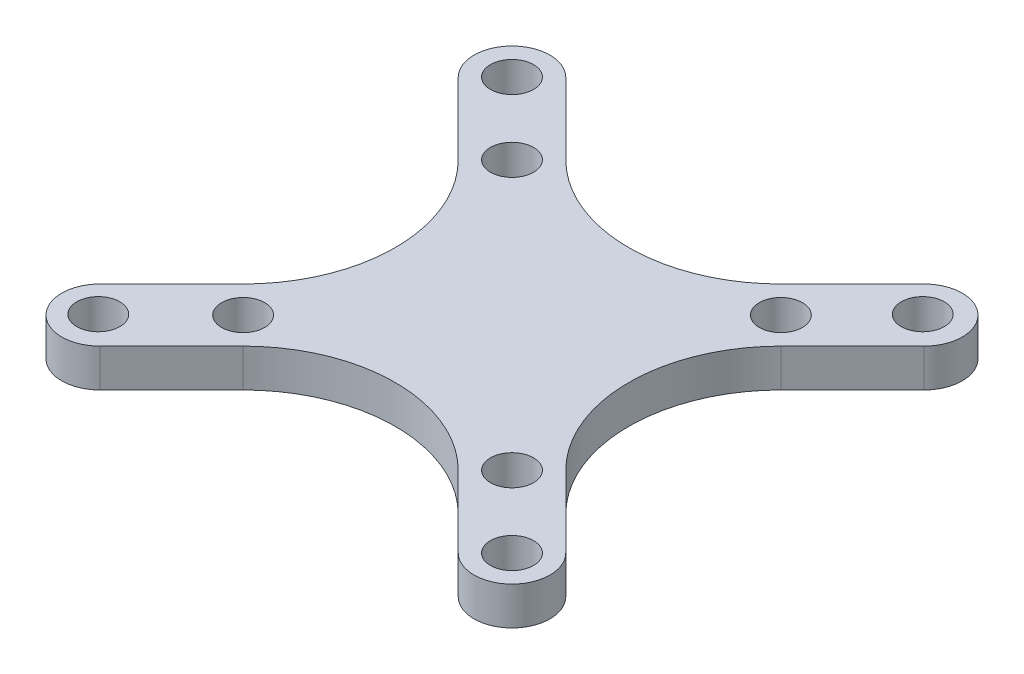
SolidWorks part; units mm, degrees
ref_plane "Front Plane" through (0, 0, 0) normal (0, 0, 1) x (1, 0, 0)
ref_plane "Top Plane" through (0, 0, 0) normal (0, 1, 0) x (1, 0, 0)
ref_plane "Right Plane" through (0, 0, 0) normal (1, 0, 0) x (0, 0, -1)
sketch "Sketch1" plane through (0, 0, 0) normal (0, 1, 0) x (1, 0, 0)
  line L0 (-16.2635, 16.2635) -> (16.2635, -16.2635) construction
  line L1 (16.1474, 16.2635) -> (-16.3795, -16.2635) construction
  line L2 (-18.3848, 14.1421) -> (-12.7279, 8.4853)
  line L3 (14.1421, 18.3848) -> (8.4853, 12.7279)
  line L4 (-14.1421, 18.3848) -> (-8.4853, 12.7279)
  line L5 (18.3848, 14.1421) -> (12.7279, 8.4853)
  line L6 (-12.7279, -8.4853) -> (-18.3848, -14.1421)
  line L7 (8.4853, -12.7279) -> (14.1421, -18.3848)
  line L8 (-8.4853, -12.7279) -> (-14.1421, -18.3848)
  line L9 (12.7279, -8.4853) -> (18.3848, -14.1421)
  line L10 (-18.3848, 18.3848) -> (-35, 35) construction
  line L11 (-25, -35) -> (25, -35)
  line L12 (-35, -25) -> (-35, 25)
  line L13 (-25, 35) -> (25, 35)
  line L14 (35, -25) -> (35, 25)
  line L15 (-35, -35) -> (35, 35) construction
  line L16 (-35, 35) -> (35, -35) construction
  line L17 (0, 35) -> (-21.6769, 28.2534)
  line L18 (-28.2534, 21.6769) -> (-35, 0)
  line L19 (-18.3848, -18.3848) -> (-35, -35) construction
  line L20 (35, -35) -> (18.3848, -18.3848) construction
  line L21 (35, 35) -> (18.3848, 18.3848) construction
  line L22 (-35, 0) -> (-28.2534, -21.6769)
  line L23 (-21.6769, -28.2534) -> (0, -35)
  line L24 (0, -35) -> (21.6769, -28.2534)
  line L25 (28.2534, -21.6769) -> (35, 0)
  line L26 (35, 0) -> (28.2534, 21.6769)
  line L27 (21.6769, 28.2534) -> (0, 35)
  circle A0 centre (-16.3795, -16.2635) radius 1.7
  circle A1 centre (-10.6066, -10.6066) radius 1.7
  circle A2 centre (16.2635, -16.2635) radius 1.7
  circle A3 centre (10.6066, -10.6066) radius 1.7
  circle A16 centre (16.1474, 16.2635) radius 1.7
  circle A17 centre (10.6066, 10.6066) radius 1.7
  circle A18 centre (-16.2635, 16.2635) radius 1.7
  circle A19 centre (-10.6066, 10.6066) radius 1.7
  arc A20 (-18.3848, 14.1421) -> (-14.1421, 18.3848) centre (-16.2635, 16.2635) cw
  arc A21 (14.1421, 18.3848) -> (18.3848, 14.1421) centre (16.2635, 16.2635) cw
  arc A22 (14.1421, -18.3848) -> (18.3848, -14.1421) centre (16.2635, -16.2635) ccw
  arc A23 (-14.1421, -18.3848) -> (-18.3848, -14.1421) centre (-16.2635, -16.2635) cw
  arc A24 (8.4853, 12.7279) -> (-8.4853, 12.7279) centre (0, 21.2132) cw
  arc A25 (-12.7279, -8.4853) -> (-12.7279, 8.4853) centre (-21.2132, 0) ccw
  arc A26 (12.7279, 8.4853) -> (12.7279, -8.4853) centre (21.2132, 0) ccw
  arc A27 (8.4853, -12.7279) -> (-8.4853, -12.7279) centre (0, -21.2132) ccw
  arc A29 (-25, -35) -> (-35, -25) centre (-25, -25) cw
  arc A30 (25, -35) -> (35, -25) centre (25, -25) ccw
  arc A31 (25, 35) -> (35, 25) centre (25, 25) cw
  arc A32 (-35, 25) -> (-25, 35) centre (-25, 25) cw
  arc A33 (-28.2534, -21.6769) -> (-21.6769, -28.2534) centre (-18.7052, -18.7052) ccw
  arc A34 (21.6769, -28.2534) -> (28.2534, -21.6769) centre (18.7052, -18.7052) ccw
  arc A35 (28.2534, 21.6769) -> (21.6769, 28.2534) centre (18.7052, 18.7052) ccw
  arc A36 (-21.6769, 28.2534) -> (-28.2534, 21.6769) centre (-18.7052, 18.7052) ccw
  point P36 (0, 0)
  point P67 (18.779, 17.8981)
  point P80 (-26.6924, -26.6924)
  point P83 (26.6924, -26.6924)
  point P86 (26.6924, 26.6924)
  point P89 (-26.6924, 26.6924)
  point P90 (0, 0)
  point P91 (0, 0)
  point P92 (0, 0)
  dimension "D1" = 37.7487
  dimension "D2" = 70
  dimension "D3" = 70
  dimension "D4" = 37.7487
  dimension "D8" = 10
  dimension "D9" = 10
  dimension "D5" = 37.7487
  dimension "D6" = 37.7487
  dimension "D7" = 27.9553
extrude "Boss-Extrude1" add sketch "Sketch1" along normal blind 3 contours A27 L7 A22 L9 A26 L5 A21 L3 A24 L4 A20 L2 A25 L6 A23 L8 A19 A18 A17 A16 A3 A2 A1 A0 | A18 | A17 | A16 | A3 | A2 | A1 | A19 | A0 region at (0.0034, 0, 0) region at (-10.6066, 0, 10.6066) region at (16.2635, 0, 16.2635) region at (10.6066, 0, 10.6066) region at (16.1474, 0, -16.2635) region at (10.6066, 0, -10.6066) region at (-16.2635, 0, -16.2635)
sketch "Sketch9" plane through (0, 3, 0) normal (0, 1, 0) x (1, 0, 0)
  point P0 (-16.3795, -16.2635)
  point P2 (-10.6066, -10.6066)
  point P4 (16.2635, -16.2635)
  point P6 (10.6066, -10.6066)
  point P8 (16.1474, 16.2635)
  point P10 (10.6066, 10.6066)
  point P12 (-10.6066, 10.6066)
  point P14 (-16.2635, 16.2635)
hole_wizard "M3 Clearance Hole3" positions "Sketch9" profile "Sketch10" hole size "M3" standard "ISO" end condition through all
sketch "Sketch10" plane through (-16.3795, 3, 16.2635) normal (1, 0, 0) x (0, 0, 1)
  line L0 (0, 0) -> (0, 3)
  line L1 (0, 3) -> (1.7, 3)
  line L2 (1.7, 3) -> (1.7, 0)
  line L5 (1.7, 0) -> (0, 0)
  line L11 (0, -6.35) -> (0, 107.95) construction
  dimension "Thru Hole Dia." = 3.4
  dimension "Thru Hole Depth" = 3
